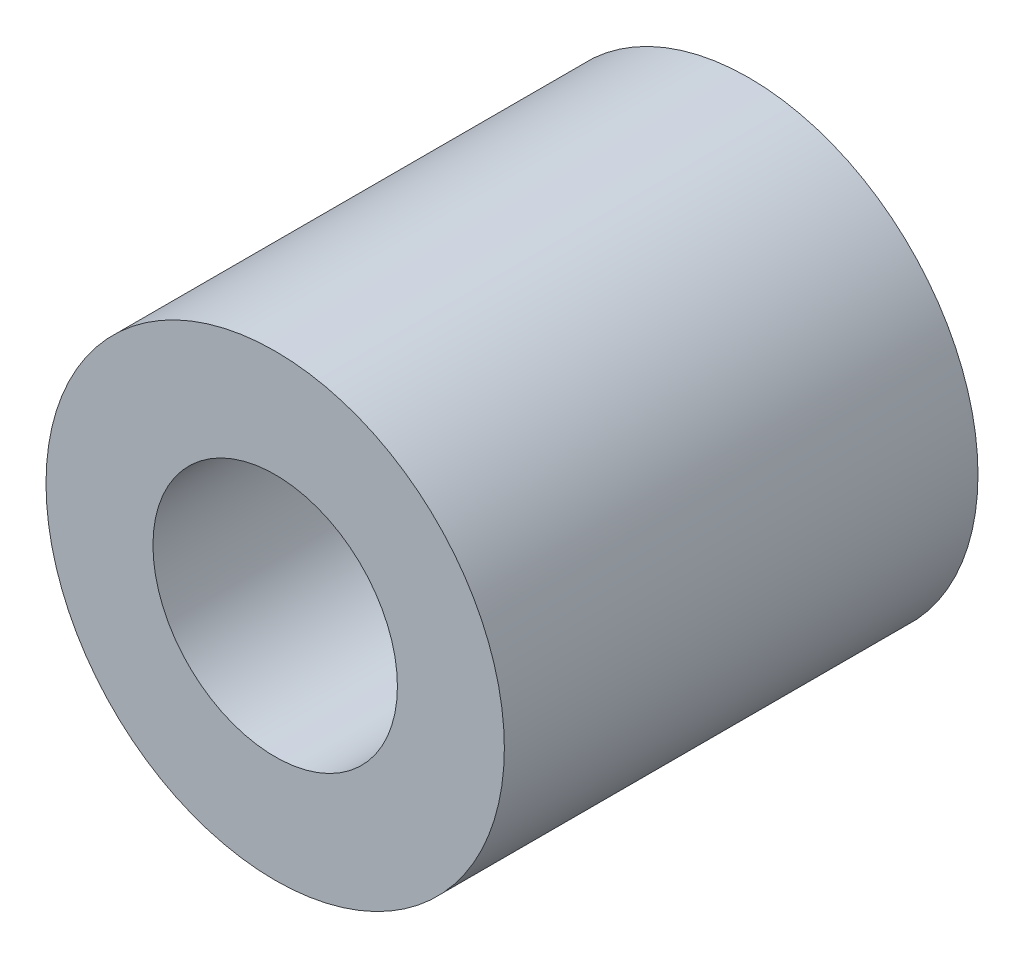
SolidWorks part; units mm, degrees
ref_plane "Front Plane" through (0, 0, 0) normal (0, 0, 1) x (1, 0, 0)
ref_plane "Top Plane" through (0, 0, 0) normal (0, 1, 0) x (1, 0, 0)
ref_plane "Right Plane" through (0, 0, 0) normal (1, 0, 0) x (0, 0, -1)
sketch "Sketch1" plane through (0, 0, 0) normal (0, 0, 1) x (1, 0, 0)
  circle A0 centre (0, 0) radius 15
  dimension "D1" = 30
extrude "Boss-Extrude1" add sketch "Sketch1" along normal blind 18
sketch "Sketch2" plane through (0, 0, 0) normal (0, 0, -1) x (-1, 0, 0)
  circle A0 centre (0, 0) radius 10
extrude "Cut-Extrude1" cut sketch "Sketch2" against normal blind 6.66
sketch "Sketch3" plane through (0, 0, 18) normal (0, 0, 1) x (1, 0, 0)
  circle A0 centre (0, 0) radius 8
extrude "Cut-Extrude2" cut sketch "Sketch3" against normal blind 100
chamfer "Chamfer1" distance 2 angle 80 1 edges at (-8, 0, 6.66) first distance on face at (-8, 0, 6.66)
sketch "Sketch4" plane through (0, 0, 18) normal (0, 0, 1) x (1, 0, 0)
  circle A0 centre (0, 0) radius 8.0005
  circle A1 centre (0, 0) radius 15
extrude "Boss-Extrude2" add sketch "Sketch4" along normal blind 13
